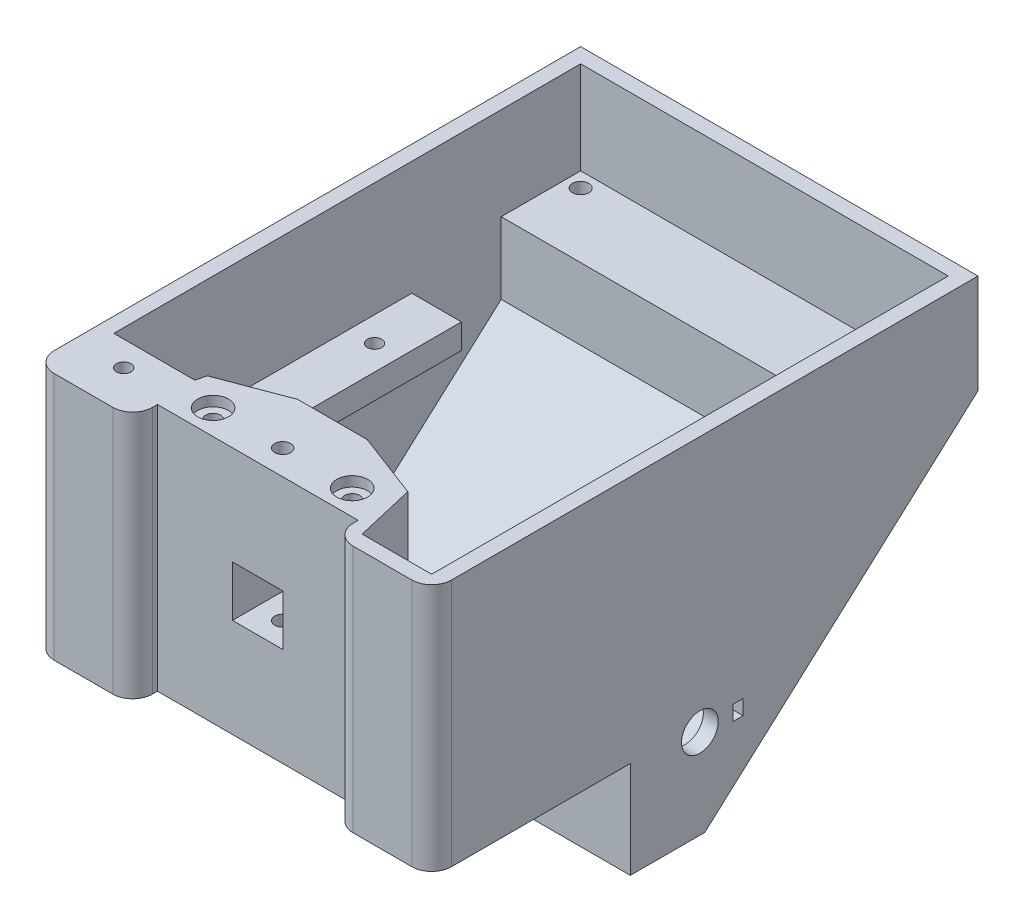
SolidWorks part; units mm, degrees
ref_plane "Спереди" through (0, 0, 0) normal (0, 0, 1) x (1, 0, 0)
ref_plane "Сверху" through (0, 0, 0) normal (0, 1, 0) x (1, 0, 0)
ref_plane "Справа" through (0, 0, 0) normal (1, 0, 0) x (0, 0, -1)
sketch "Sketch2" plane through (0, 0, 0) normal (1, 0, 0) x (0, 0, -1)
  line L0 (-27.3205, 20.9982) -> (-27.3205, -29.0018)
  line L1 (-27.3205, -29.0018) -> (12.6795, -29.0018)
  line L2 (12.6795, -29.0018) -> (12.6795, -48.5114)
  line L3 (12.6795, -48.5114) -> (27.6795, -48.5114)
  line L4 (82.6795, 20.9982) -> (82.6795, 0.9982)
  line L5 (82.6795, 20.9982) -> (-27.3205, 20.9982)
  line L6 (82.6795, 0.9982) -> (27.6795, -48.5114)
  dimension "D1" = 110
  dimension "D2" = 50
  dimension "D3" = 40
  dimension "D4" = 15
  dimension "D5" = 20
extrude "Boss-Extrude1" add sketch "Sketch2" along normal blind 80
shell "Shell1" thickness 3 removed face at (40, 20.9982, -27.6795)
sketch "Sketch3" plane through (0, 0, 24.3205) normal (0, 0, -1) x (-1, 0, 0)
  line L0 (-40, 20.9982) -> (-40, -26.0018) construction
  line L3 (-77, 20.9982) -> (-3, 20.9982) construction
  line L4 (-77, -26.0018) -> (-3, -26.0018) construction
  line L6 (-17, 20.9982) -> (-63, 20.9982)
  line L7 (-17, 20.9982) -> (-17, -26.0018)
  line L8 (-17, -26.0018) -> (-63, -26.0018)
  line L9 (-63, 20.9982) -> (-63, -26.0018)
  line L10 (-17, 20.9982) -> (-63, -26.0018) construction
  line L11 (-17, -26.0018) -> (-63, 20.9982) construction
  point P6 (-40, -2.5018)
  dimension "D1" = 46
extrude "Boss-Extrude2" add sketch "Sketch3" along normal blind 17
sketch "Sketch4" plane through (0, 0, 27.3205) normal (0, 0, 1) x (1, 0, 0)
  line L0 (0, 20.9982) -> (80, -29.0018) construction
  line L2 (45.1, -9.1018) -> (34.9, -9.1018)
  line L3 (45.1, -9.1018) -> (45.1, 1.0982)
  line L4 (45.1, 1.0982) -> (34.9, 1.0982)
  line L5 (34.9, -9.1018) -> (34.9, 1.0982)
  line L6 (45.1, -9.1018) -> (34.9, 1.0982) construction
  line L7 (45.1, 1.0982) -> (34.9, -9.1018) construction
  point P4 (40, -4.0018)
  dimension "D1" = 10.2
extrude "Cut-Extrude1" cut sketch "Sketch4" against normal up to surface (20 mm away) up to face at (40, -2.5018, 7.3205)
sketch "Sketch6" plane through (0, -29.0018, 0) normal (0, -1, 0) x (1, 0, 0)
  line L0 (40, 27.3205) -> (40, -12.6795) construction
  line L1 (47.5, -5.4795) -> (32.5, -5.4795)
  line L2 (47.5, -5.4795) -> (47.5, 7.3205)
  line L3 (47.5, 7.3205) -> (32.5, 7.3205)
  line L4 (32.5, -5.4795) -> (32.5, 7.3205)
  line L5 (47.5, -5.4795) -> (32.5, 7.3205) construction
  line L6 (47.5, 7.3205) -> (32.5, -5.4795) construction
  line L7 (80, -12.6795) -> (0, -12.6795) construction
  line L9 (80, 27.3205) -> (0, 27.3205) construction
  point P0 (40, 0.9205)
  dimension "D1" = 15
  dimension "D2" = 12.8
  dimension "D4" = 20
extrude "Cut-Extrude2" cut sketch "Sketch6" against normal up to surface (3 mm away) up to face at (40, -26.0018, 10.0705)
sketch "Sketch7" plane through (0, 0, 27.3205) normal (0, 0, 1) x (1, 0, 0)
  line L0 (40, 20.9982) -> (40, -29.0018) construction
  line L1 (80, 20.9982) -> (0, 20.9982) construction
  line L2 (80, -29.0018) -> (0, -29.0018) construction
  line L4 (60.2, -29.0018) -> (19.8, -29.0018)
  line L5 (60.2, -29.0018) -> (60.2, 20.9982)
  line L6 (60.2, 20.9982) -> (19.8, 20.9982)
  line L7 (19.8, -29.0018) -> (19.8, 20.9982)
  line L8 (60.2, -29.0018) -> (19.8, 20.9982) construction
  line L9 (60.2, 20.9982) -> (19.8, -29.0018) construction
  point P6 (40, -4.0018)
  dimension "D1" = 40.4
extrude "Cut-Extrude3" cut sketch "Sketch7" against normal blind 5
fillet "Fillet1" radius 4 4 edges at (19.8, -4.0018, 27.3205) (60.2, -4.0018, 27.3205) (80, -4.0018, 27.3205) (0, -4.0018, 27.3205)
sketch "Sketch12" plane through (0, 20.9982, 0) normal (0, 1, 0) x (1, 0, 0)
  line L0 (19.8, -22.3205) -> (19.8, -12.3205) construction
  line L1 (19.8, -12.3205) -> (60.2, -12.3205) construction
  line L2 (60.2, -12.3205) -> (60.2, -22.3205) construction
  line L3 (33, -7.3205) -> (19.8, -12.3205)
  line L4 (17, -7.3205) -> (63, -7.3205) construction
  line L5 (19.8, -12.3205) -> (17, -24.3205)
  line L6 (17, -24.3205) -> (17, -7.3205)
  line L7 (17, -7.3205) -> (33, -7.3205)
  line L8 (47, -7.3205) -> (63, -7.3205)
  line L9 (63, -7.3205) -> (63, -24.3205)
  line L10 (63, -24.3205) -> (60.2, -12.3205)
  line L11 (60.2, -12.3205) -> (47, -7.3205)
  dimension "D1" = 10
  dimension "D2" = 16
extrude "Cut-Extrude7" cut sketch "Sketch12" against normal up to surface (47 mm away) up to face at (40, -26.0018, 7.0205)
sketch "Sketch13" plane through (0, 20.9982, 0) normal (0, 1, 0) x (1, 0, 0)
  line L0 (19.8, -22.3205) -> (19.8, -12.3205) construction
  line L1 (19.8, -12.3205) -> (60.2, -12.3205) construction
  line L2 (60.2, -12.3205) -> (60.2, -22.3205) construction
  line L3 (60.2, -17.3205) -> (19.8, -17.3205) construction
  circle A0 centre (26, -17.3205) radius 1.5
  circle A1 centre (54, -17.3205) radius 1.5
  point P14 (40, -17.3205)
  dimension "D1" = 3
  dimension "D2" = 28
  dimension "D3" = 14
  dimension "D4" = 6.2
extrude "Cut-Extrude8" cut sketch "Sketch13" against normal blind 25
sketch "Sketch14" plane through (0, 20.9982, 0) normal (0, 1, 0) x (1, 0, 0)
  circle A0 centre (26, -17.3205) radius 3.1
  circle A1 centre (54, -17.3205) radius 3.1
  dimension "D1" = 6.2
extrude "Cut-Extrude9" cut sketch "Sketch14" against normal blind 2
sketch "Sketch17" plane through (77, 0, 0) normal (-1, 0, 0) x (0, 0, 1)
  line L0 (-45.6795, -2.0018) -> (-0.6795, -2.0018)
  line L1 (-0.6795, -2.0018) -> (-0.6795, -7.0018)
  line L2 (-0.6795, -7.0018) -> (-45.6795, -7.0018)
  line L3 (-45.6795, -7.0018) -> (-45.6795, -2.0018)
  line L4 (-79.6795, 20.9982) -> (24.3205, 20.9982) construction
  line L5 (-79.6795, 2.3342) -> (-79.6795, 20.9982) construction
  dimension "D1" = 45
  dimension "D2" = 5
  dimension "D3" = 23
  dimension "D4" = 34
extrude "Boss-Extrude5" add sketch "Sketch17" along normal up to surface (74 mm away) up to face at (3, -14.0994, -24.0865)
sketch "Sketch18" plane through (0, -2.0018, 0) normal (0, 1, 0) x (1, 0, 0)
  line L0 (40, 0.6795) -> (40, 45.6795) construction
  line L1 (3, 0.6795) -> (77, 0.6795) construction
  line L2 (3, 45.6795) -> (77, 45.6795) construction
  line L3 (77, 0.6795) -> (77, 45.6795) construction
  line L4 (13, 0.6795) -> (67, 0.6795)
  line L5 (13, 0.6795) -> (13, 45.6795)
  line L6 (13, 45.6795) -> (67, 45.6795)
  line L7 (67, 0.6795) -> (67, 45.6795)
  line L8 (13, 0.6795) -> (67, 45.6795) construction
  line L9 (13, 45.6795) -> (67, 0.6795) construction
  point P6 (40, 23.1795)
  dimension "D1" = 10
extrude "Cut-Extrude10" cut sketch "Sketch18" against normal up to next
sketch "Sketch19" plane through (0, -2.0018, 0) normal (0, 1, 0) x (1, 0, 0)
  line L0 (72, 45.6795) -> (72, 0.6795) construction
  line L1 (67, 45.6795) -> (77, 45.6795) construction
  line L2 (67, 0.6795) -> (77, 0.6795) construction
  line L3 (8, 45.6795) -> (8, 0.6795) construction
  line L4 (3, 45.6795) -> (13, 45.6795) construction
  line L5 (3, 0.6795) -> (13, 0.6795) construction
  circle A0 centre (72, 37.1795) radius 1.45
  circle A1 centre (72, 6.1795) radius 1.45
  circle A2 centre (8, 33.1795) radius 1.45
  circle A3 centre (8, 6.1795) radius 1.45
  point P20 (72, 23.1795)
  point P21 (8, 23.1795)
  dimension "D1" = 2.9
  dimension "D2" = 14
  dimension "D3" = 17
  dimension "D4" = 17
  dimension "D5" = 10
extrude "Cut-Extrude11" cut sketch "Sketch19" against normal up to next
sketch "Sketch21" plane through (0, -26.0018, 0) normal (0, 1, 0) x (1, 0, 0)
  line L0 (3, -24.3205) -> (3, -14.3205)
  line L1 (3, -24.3205) -> (3, 15.6795) construction
  line L2 (3, -14.3205) -> (19.3333, -14.3205)
  line L3 (19.8, -12.3205) -> (17, -24.3205) construction
  line L4 (19.3333, -14.3205) -> (17, -24.3205)
  line L6 (3, -24.3205) -> (17, -24.3205)
  dimension "D1" = 10
extrude "Boss-Extrude6" add sketch "Sketch21" along normal up to surface (47 mm away) up to face at (54, 20.9982, 20.4205)
sketch "Sketch22" plane through (0, 20.9982, 0) normal (0, 1, 0) x (1, 0, 0)
  line L0 (0, 82.6795) -> (0, -23.3205) construction
  line L1 (15.8, -27.3205) -> (4, -27.3205) construction
  circle A0 centre (10, -19.3205) radius 1.45
  dimension "D1" = 2.9
  dimension "D2" = 10
  dimension "D3" = 8
extrude "Cut-Extrude12" cut sketch "Sketch22" against normal through all
sketch "Sketch24" plane through (80, 0, 0) normal (1, 0, 0) x (0, 0, -1)
  line L0 (12.6795, -48.5114) -> (27.6795, -48.5114) construction
  line L1 (12.6795, -29.0018) -> (12.6795, -48.5114) construction
  line L2 (18.1795, -30.5114) -> (18.1795, -19.0114) construction
  line L3 (18.1795, -19.0114) -> (35.1795, -19.0114) construction
  line L4 (35.1795, -19.0114) -> (35.1795, -30.5114) construction
  line L5 (26.6795, -19.0114) -> (26.6795, -39.0114) construction
  line L6 (30.3795, -30.5114) -> (34.3795, -30.5114) construction
  line L8 (33.3795, -32.0114) -> (35.3795, -32.0114)
  line L9 (33.3795, -32.0114) -> (33.3795, -29.0114)
  line L10 (33.3795, -29.0114) -> (35.3795, -29.0114)
  line L11 (35.3795, -32.0114) -> (35.3795, -29.0114)
  line L12 (33.3795, -32.0114) -> (35.3795, -29.0114) construction
  line L13 (33.3795, -29.0114) -> (35.3795, -32.0114) construction
  circle A0 centre (26.6795, -30.5114) radius 3.7
  circle A1 centre (26.6795, -30.5114) radius 8.5 construction
  dimension "D1" = 7.4
  dimension "D2" = 17
  dimension "D3" = 18
  dimension "D4" = 14
  dimension "D5" = 20
  dimension "D6" = 4
  dimension "D7" = 2
  dimension "D8" = 3
extrude "Cut-Extrude13" cut sketch "Sketch24" against normal up to next
sketch "Sketch26" plane through (3, 0, 0) normal (1, 0, 0) x (0, 0, -1)
  line L0 (79.6795, 2.3342) -> (63.6795, 2.3342)
  line L1 (63.6795, 2.3342) -> (63.6795, -12.0686)
  line L2 (26.5281, -45.5114) -> (79.6795, 2.3342) construction
  line L3 (63.6795, -12.0686) -> (79.6795, 2.3342)
  dimension "D1" = 16
extrude "Boss-Extrude7" add sketch "Sketch26" along normal up to surface (74 mm away) up to face at (77, -30.5114, -34.3795)
sketch "Sketch27" plane through (0, 2.3342, 0) normal (0, 1, 0) x (1, 0, 0)
  line L0 (3, 76.6795) -> (77, 76.6795) construction
  line L1 (3, 79.6795) -> (3, 63.6795) construction
  line L2 (77, 79.6795) -> (77, 63.6795) construction
  line L3 (80, 82.6795) -> (0, 82.6795) construction
  circle A0 centre (6, 76.6795) radius 1.65
  circle A1 centre (74, 76.6795) radius 1.65
  point P10 (40, 76.6795)
  dimension "D1" = 3.3
  dimension "D2" = 68
  dimension "D3" = 34
  dimension "D4" = 6
extrude "Cut-Extrude14" cut sketch "Sketch27" against normal blind 10
sketch "Sketch28" plane through (0, 2.3342, 0) normal (0, 1, 0) x (1, 0, 0)
  line L1 (74, 79.9295) -> (71.1854, 78.3045)
  line L2 (71.1854, 78.3045) -> (71.1854, 75.0545)
  line L3 (71.1854, 75.0545) -> (74, 73.4295)
  line L4 (74, 73.4295) -> (76.8146, 75.0545)
  line L5 (76.8146, 75.0545) -> (76.8146, 78.3045)
  line L6 (76.8146, 78.3045) -> (74, 79.9295)
  line L7 (6, 73.4295) -> (8.8146, 75.0545)
  line L8 (8.8146, 75.0545) -> (8.8146, 78.3045)
  line L9 (8.8146, 78.3045) -> (6, 79.9295)
  line L10 (6, 79.9295) -> (3.1854, 78.3045)
  line L11 (3.1854, 78.3045) -> (3.1854, 75.0545)
  line L12 (3.1854, 75.0545) -> (6, 73.4295)
  circle A0 centre (74, 76.6795) radius 3.25 construction
  circle A1 centre (6, 76.6795) radius 3.25 construction
  dimension "D1" = 6.5
extrude "Cut-Extrude15" cut sketch "Sketch28" against normal blind 32 from offset 3 offset against normal yes
sketch "Sketch29" plane through (0, -29.0018, 0) normal (0, -1, 0) x (1, 0, 0)
  line L0 (0, 23.3205) -> (0, -12.6795) construction
  line L1 (7.1854, 17.6955) -> (10, 16.0705)
  line L2 (10, 16.0705) -> (12.8146, 17.6955)
  line L3 (12.8146, 17.6955) -> (12.8146, 20.9455)
  line L4 (12.8146, 20.9455) -> (10, 22.5705)
  line L5 (10, 22.5705) -> (7.1854, 20.9455)
  line L6 (7.1854, 20.9455) -> (7.1854, 17.6955)
  circle A0 centre (10, 19.3205) radius 3.25 construction
  dimension "D1" = 6.5
extrude "Cut-Extrude16" cut sketch "Sketch29" against normal blind 30
sketch "Sketch30" plane through (0, -26.0018, 0) normal (0, 1, 0) x (1, 0, 0)
  line L0 (77, -24.3205) -> (63, -24.3205)
  line L1 (63, -24.3205) -> (60.2, -12.3205)
  line L2 (63, -24.3205) -> (60.2, -12.3205) construction
  line L3 (60.2, -12.3205) -> (77, -12.3205)
  line L4 (77, -24.3205) -> (77, 15.6795) construction
  line L5 (77, -12.3205) -> (77, -24.3205)
  dimension "D1" = 12
extrude "Boss-Extrude8" add sketch "Sketch30" along normal blind 20
sketch "Sketch31" plane through (0, -6.0018, 0) normal (0, 1, 0) x (1, 0, 0)
  line L0 (76, -27.3205) -> (64.2, -27.3205) construction
  line L1 (80, -23.3205) -> (80, 12.6795) construction
  circle A0 centre (72, -21.3205) radius 1.5
  dimension "D3" = 3
  dimension "D1" = 6
  dimension "D2" = 8
extrude "Cut-Extrude17" cut sketch "Sketch31" against normal through all
sketch "Sketch32" plane through (0, -29.0018, 0) normal (0, -1, 0) x (1, 0, 0)
  line L1 (72, 24.5705) -> (69.1854, 22.9455)
  line L2 (69.1854, 22.9455) -> (69.1854, 19.6955)
  line L3 (69.1854, 19.6955) -> (72, 18.0705)
  line L4 (72, 18.0705) -> (74.8146, 19.6955)
  line L5 (74.8146, 19.6955) -> (74.8146, 22.9455)
  line L6 (74.8146, 22.9455) -> (72, 24.5705)
  circle A0 centre (72, 21.3205) radius 3.25 construction
  dimension "D1" = 6.5
extrude "Cut-Extrude18" cut sketch "Sketch32" against normal blind 15
sketch "Sketch33" plane through (0, -2.0018, 0) normal (0, 1, 0) x (1, 0, 0)
  line L0 (67, 40.6795) -> (77, 40.6795)
  line L1 (67, 0.6795) -> (67, 45.6795) construction
  line L2 (77, 0.6795) -> (77, 45.6795) construction
  line L3 (77, 40.6795) -> (77, 45.6795)
  line L4 (77, 45.6795) -> (67, 45.6795)
  line L5 (67, 45.6795) -> (67, 40.6795)
  dimension "D1" = 5
extrude "Cut-Extrude19" cut sketch "Sketch33" against normal up to next
sketch "Sketch34" plane through (0, 20.9982, 0) normal (0, 1, 0) x (1, 0, 0)
  line L0 (54, -17.3205) -> (26, -17.3205) construction
  circle A0 centre (40, -17.3205) radius 1.6
  dimension "D1" = 3.2
extrude "Cut-Extrude20" cut sketch "Sketch34" against normal through all
sketch "Sketch36" plane through (0, -29.0018, 0) normal (0, -1, 0) x (1, 0, 0)
  line L1 (38.375, 20.1351) -> (36.75, 17.3205)
  line L2 (36.75, 17.3205) -> (38.375, 14.5059)
  line L3 (38.375, 14.5059) -> (41.625, 14.5059)
  line L4 (41.625, 14.5059) -> (43.25, 17.3205)
  line L5 (43.25, 17.3205) -> (41.625, 20.1351)
  line L6 (41.625, 20.1351) -> (38.375, 20.1351)
  circle A0 centre (40, 17.3205) radius 3.25 construction
  dimension "D1" = 6.5
extrude "Cut-Extrude22" cut sketch "Sketch36" against normal blind 14
